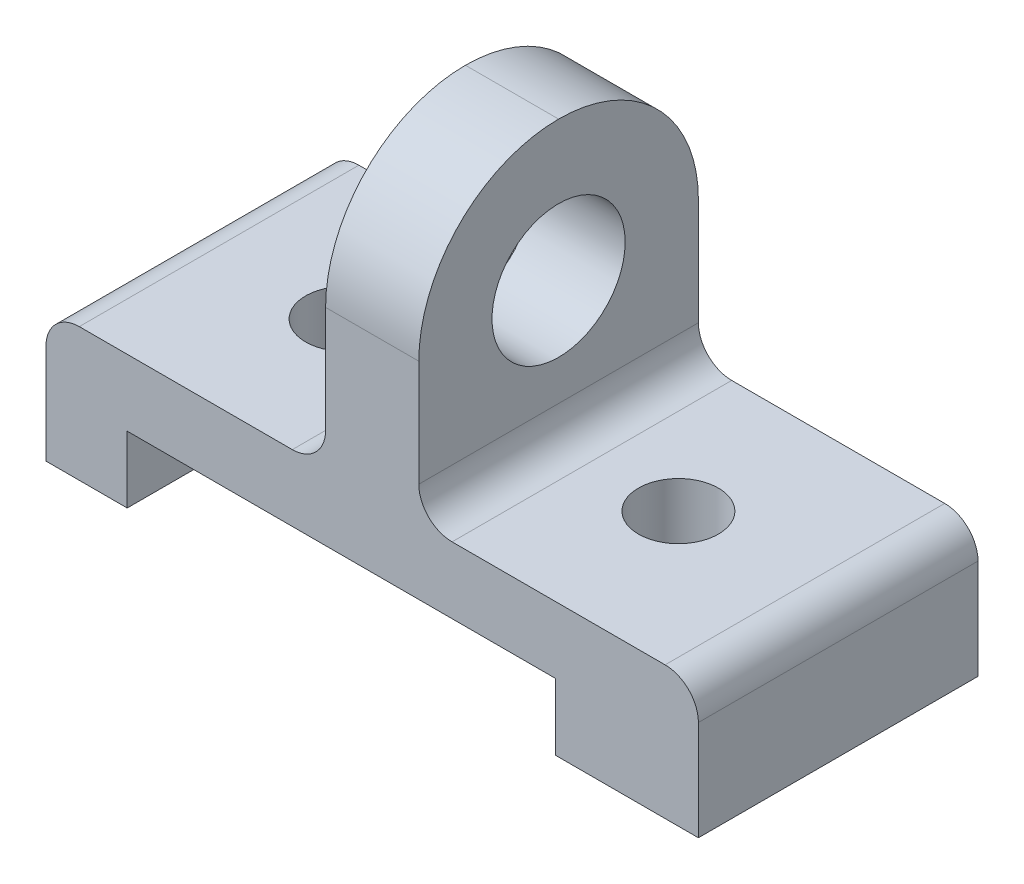
SolidWorks part; units mm, degrees
ref_plane "Front Plane" through (0, 0, 0) normal (0, 0, 1) x (1, 0, 0)
ref_plane "Top Plane" through (0, 0, 0) normal (0, 1, 0) x (1, 0, 0)
ref_plane "Right Plane" through (0, 0, 0) normal (1, 0, 0) x (0, 0, -1)
sketch "Sketch2" plane through (0, 0, 0) normal (0, 1, 0) x (1, 0, 0)
  line L1 (0, 0) -> (98, 0)
  line L2 (0, 0) -> (0, 42)
  line L3 (0, 42) -> (98, 42)
  line L4 (98, 0) -> (98, 42)
  dimension "D1" = 98
  dimension "D2" = 42
extrude "Boss-Extrude1" add sketch "Sketch2" along normal mid plane 20
sketch "Sketch3" plane through (0, 0, 0) normal (0, 0, 1) x (1, 0, 0)
  line L0 (0, -10) -> (98, -10) construction
  line L1 (12.1991, -10) -> (76.5282, -10)
  line L2 (12.1991, -10) -> (12.1991, 0)
  line L3 (12.1991, 0) -> (76.5282, 0)
  line L4 (76.5282, -10) -> (76.5282, 0)
extrude "Cut-Extrude3" cut sketch "Sketch3" against normal through all contours L2 L3 L4 L1
ref_plane "Plane2" through (49, 0, 0) normal (1, 0, 0) x (0, 0, -1)
sketch "Sketch4" plane through (49, 0, 0) normal (1, 0, 0) x (0, 0, -1)
  line L1 (0, 10) -> (42, 10)
  line L2 (0, 10) -> (0, 52)
  line L3 (0, 52) -> (42, 52)
  line L4 (42, 10) -> (42, 52)
  dimension "D1" = 42
  dimension "D2" = 42
extrude "Boss-Extrude2" add sketch "Sketch4" along normal mid plane 14
fillet "Fillet1" radius 21 2 edges at (49, 52, 0) (49, 52, -42)
sketch "Sketch5" plane through (56, 0, 0) normal (1, 0, 0) x (0, 0, -1)
  line L0 (0, 10) -> (42, 10) construction
  circle A0 centre (21, 31) radius 10
  dimension "D1" = 20
  dimension "D2" = 21
extrude "Cut-Extrude4" cut sketch "Sketch5" against normal blind 14
sketch "Sketch7" plane through (0, 10, 0) normal (0, 1, 0) x (1, 0, 0)
  line L0 (0, 0) -> (42, 0) construction
  line L1 (0, 42) -> (0, 0) construction
  circle A0 centre (24, 21) radius 6
  dimension "D1" = 12
  dimension "D2" = 21
  dimension "D3" = 24
extrude "Cut-Extrude6" cut sketch "Sketch7" against normal through all
mirror "Mirror3" about plane through (49, 0, 0) normal (1, 0, 0) of "Cut-Extrude6"
fillet "Fillet5" radius 5 1 edges at (98, 10, -21)
fillet "Fillet6" radius 5 1 edges at (0, 10, -21)
fillet "Fillet7" radius 5 2 edges at (42, 10, -21) (56, 10, -21)
